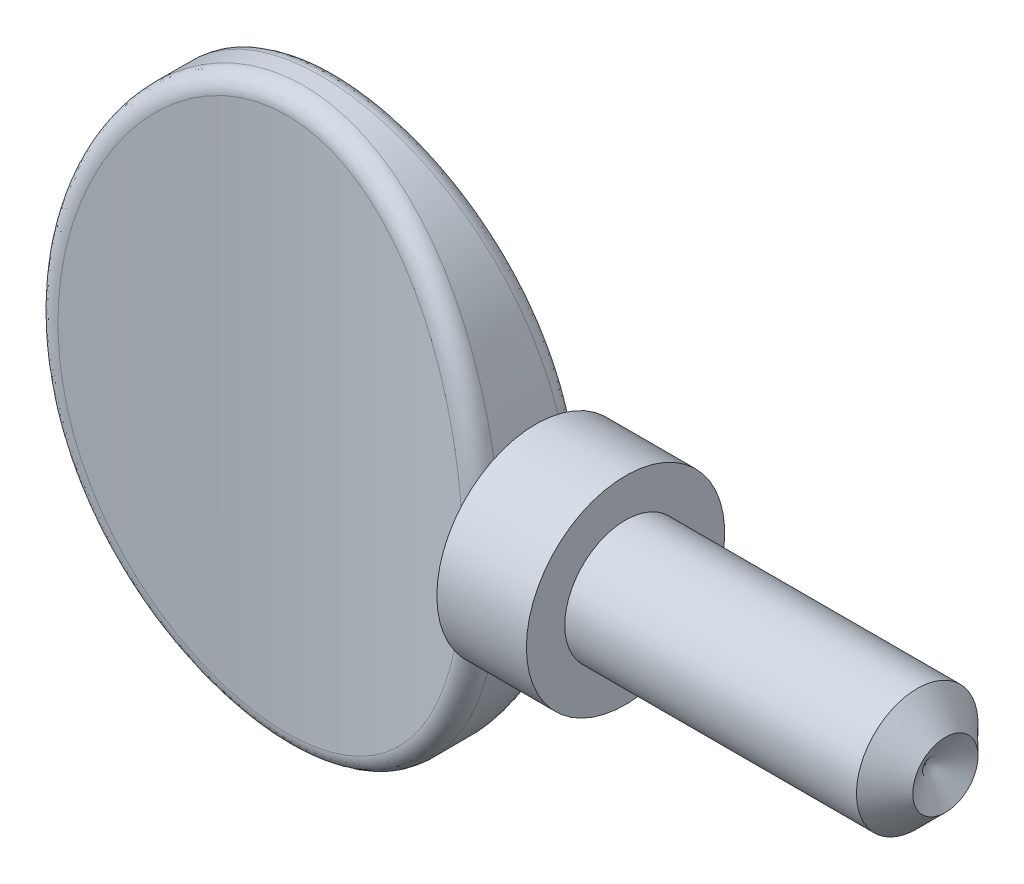
SolidWorks part; units mm, degrees
ref_plane "Front" through (0, 0, 0) normal (0, 0, 1) x (1, 0, 0)
ref_plane "Top" through (0, 0, 0) normal (0, 1, 0) x (1, 0, 0)
ref_plane "Right" through (0, 0, 0) normal (1, 0, 0) x (0, 0, -1)
ref_axis "Axis1" through (-50, 0, 0) along (1, 0, 0)
sketch "Sketch1" plane through (0, 0, 0) normal (0, 0, 1) x (1, 0, 0)
  line L0 (0, 0) -> (25.146, 0) construction
  line L1 (12.446, -3.937) -> (12.446, 3.937)
  ellipse E0 centre (0, 0) end of major axis (0, 11.303) minor radius 8.89
  dimension "D2" = 3.556
extrude "Extrude1" add sketch "Sketch1" along normal mid plane 4.572
sketch "Sketch2" plane through (0, 0, 0) normal (0, 1, 0) x (1, 0, 0)
  line L0 (8.89, 2.286) -> (-8.89, 2.286) construction
  line L1 (0, 0) -> (0, 1.1721) construction
  line L2 (-1.7991, 0) -> (2.0444, 0) construction
  line L3 (-8.89, -2.286) -> (8.89, -2.286) construction
  line L6 (-8.89, 2.286) -> (-8.89, -2.286)
  line L7 (8.89, 2.286) -> (8.89, -2.286)
  arc A0 (-8.89, 2.286) -> (8.89, 2.286) centre (0, 32.766) ccw
  arc A1 (-8.89, -2.286) -> (8.89, -2.286) centre (0, -32.766) cw
extrude "Cut-Extrude1" cut sketch "Sketch2" against normal through all and the other way through all flip side to cut
fillet "Fillet3" radius 0.6773 2 edges at (-8.875, -0.6558, 2.2816) (-1.5369, -11.1328, -1.0532)
sketch "Sketch3" plane through (0, 0, 0) normal (0, 1, 0) x (1, 0, 0)
  line L0 (12.446, 3.937) -> (12.446, 2.413)
  line L1 (0, 0) -> (21.0288, 0) construction
  line L2 (0, 0) -> (25.146, 0) construction
  line L3 (12.446, 2.413) -> (12.446, 0) construction
  line L4 (12.446, 2.413) -> (24.0284, 2.413)
  line L5 (25.146, 1.2954) -> (24.3676, 0)
  line L6 (12.446, 3.937) -> (8.89, 3.937)
  line L7 (7.2364, 1.8517) -> (7.2364, 0)
  line L8 (8.89, 0) -> (8.89, 3.937) construction
  line L9 (7.2364, 0) -> (24.3676, 0)
  line L10 (25.146, 1.2954) -> (24.0284, 2.413)
  arc A0 (8.89, 3.937) -> (7.2364, 1.8517) centre (6.7483, 3.937) cw
  arc A3 (-8.89, 2.286) -> (8.89, 2.286) centre (0, 32.766) ccw construction
  dimension "D1" = 7.874
  dimension "D2" = 45
  dimension "D3" = 59
revolve "Revolve1" add sketch "Sketch3" angle 360 about L0
cosmetic thread "Cosmetic Thread1" [suppressed]
sketch "Sketch4" plane through (0, 0, 0) normal (0, 0, 1) x (1, 0, 0)
  line L0 (0, 0) -> (27.7993, 0) construction
  line L1 (23.6295, 2.413) -> (24.0284, 1.7221)
  line L2 (24.0284, 1.7221) -> (24.4273, 2.413)
  line L3 (24.4273, 2.413) -> (24.4273, 3.2108)
  line L4 (24.4273, 3.2108) -> (23.6295, 3.2108)
  line L5 (23.6295, 3.2108) -> (23.6295, 2.413)
  line L6 (24.0284, 2.413) -> (24.0284, -2.413) construction
  dimension "D1" = 3.4442
  dimension "D2" = 4.826
revolve "Cut-Revolve10" [suppressed] cut sketch "Sketch4" angle 360 about L0
pattern_linear "LPattern10" [suppressed] count 11 along (-1, 0, 0) of bodies 109
equation "\"D2@Sketch1\" = \"B@Sketch1\" / 6"
equation "\"D1@Sketch3\" = \"E@Sketch1\""
equation "\"D1@Fillet3\" = \"C1@Sketch2\" / 3"
equation "\"D1@Sketch4\" = \"D2@Cosmetic Thread1\""
equation "\"D2@Sketch4\" = \"DIA@Sketch3\""
equation "\"D1@LPattern10\" = (  \"L@Sketch1\"  -  ( \"DIA@Sketch3\" - \"cup_dia@Sketch3\" )  / 2 ) / \"P@LPattern10\" "
